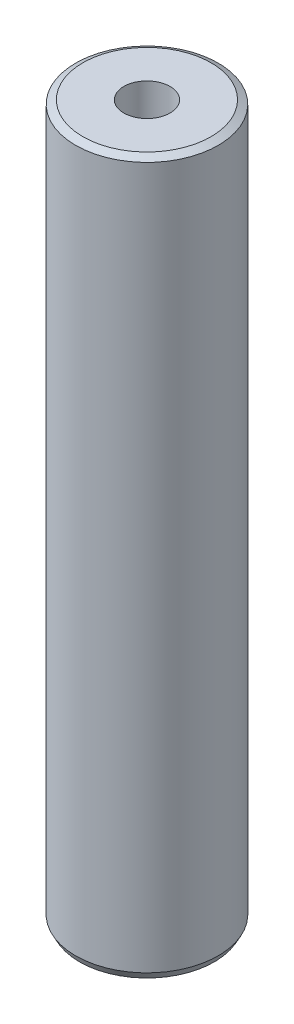
SolidWorks part; units mm, degrees
ref_plane "Front Plane" through (0, 0, 0) normal (0, 0, 1) x (1, 0, 0)
ref_plane "Top Plane" through (0, 0, 0) normal (0, 1, 0) x (1, 0, 0)
ref_plane "Right Plane" through (0, 0, 0) normal (1, 0, 0) x (0, 0, -1)
sketch "Sketch1" plane through (0, 0, 0) normal (0, 1, 0) x (1, 0, 0)
  circle A0 centre (0, 0) radius 60
  dimension "SHAFT_OD" = 120
extrude "Boss-Extrude1" add sketch "Sketch1" along normal blind 600
sketch "Sketch2" plane through (0, 0, 0) normal (0, 1, 0) x (1, 0, 0)
  circle A0 centre (0, 0) radius 19.4288
  dimension "BORE_D" = 38.8577
extrude "Cut-Extrude1" cut sketch "Sketch2" along normal through all
chamfer "Chamfer1" distance 3.2683 angle 61.723 2 edges at (0, 600, 60) (0, 0, 60) first distance on face at (0, 600, 60) first distance on face at (0, 0, 19.4288)
